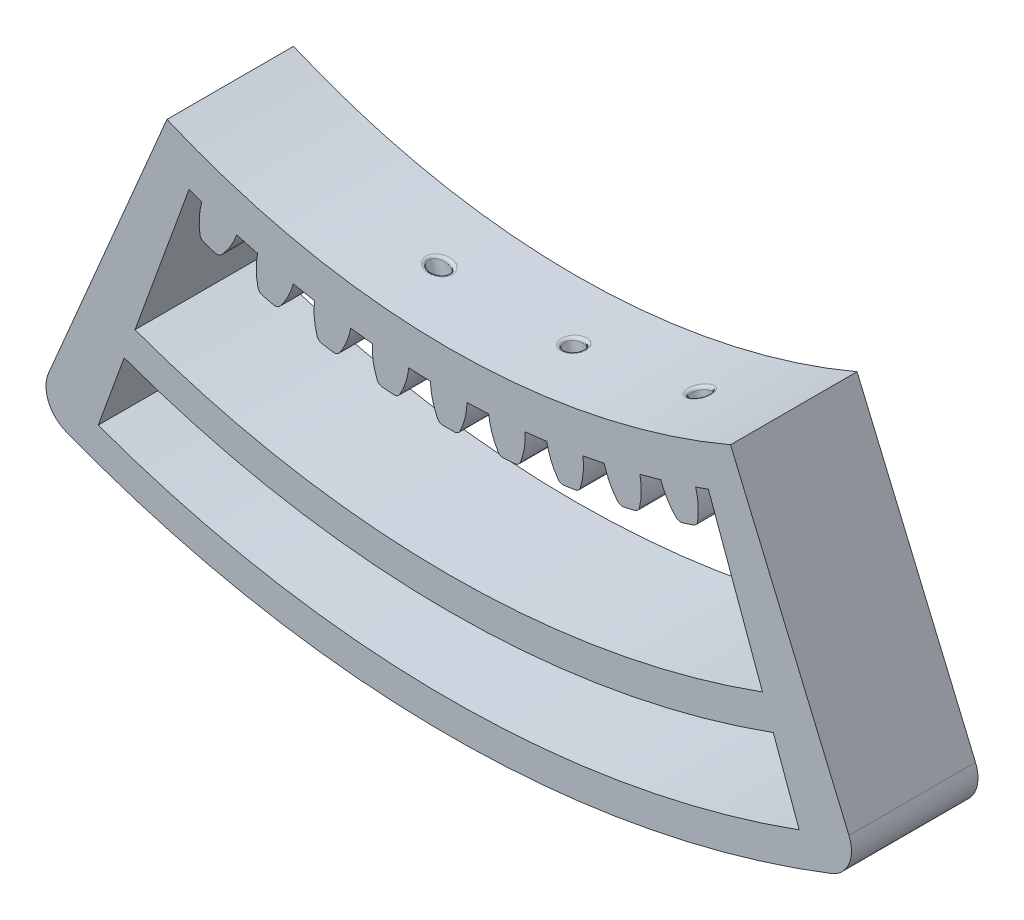
SolidWorks part; units mm, degrees
material "ABS PC"
ref_plane "Plan de face" through (0, 0, 0) normal (0, 0, 1) x (1, 0, 0)
ref_plane "Plan de dessus" through (0, 0, 0) normal (0, 1, 0) x (1, 0, 0)
ref_plane "Plan de droite" through (0, 0, 0) normal (1, 0, 0) x (0, 0, -1)
sketch "Esquisse1" plane through (0, 0, 0) normal (0, 0, 1) x (1, 0, 0)
  line L0 (-49.5929, -136.2554) -> (-41.0424, -112.7631)
  line L1 (41.0424, -112.7631) -> (49.5929, -136.2554)
  line L2 (0, 0) -> (0, -167) construction
  line L3 (-65.2521, -153.7243) -> (-44.5433, -104.9376)
  line L4 (44.5433, -104.9376) -> (65.2521, -153.7243)
  line L5 (51.303, -140.9539) -> (55.4073, -152.2302)
  line L6 (-51.303, -140.9539) -> (-55.4073, -152.2302)
  arc A0 (-65.2521, -153.7243) -> (65.2521, -153.7243) centre (0, 0) ccw
  arc A1 (-44.5433, -104.9376) -> (44.5433, -104.9376) centre (0, 0) ccw
  arc A2 (-41.0424, -112.7631) -> (41.0424, -112.7631) centre (0, 0) ccw
  arc A3 (-49.5929, -136.2554) -> (49.5929, -136.2554) centre (0, 0) ccw
  arc A4 (-55.4073, -152.2302) -> (55.4073, -152.2302) centre (0, 0) ccw
  arc A5 (-51.303, -140.9539) -> (51.303, -140.9539) centre (0, 0) ccw
  point P1 (-46.8877, -110.4606)
  point P21 (59.0684, -126.6805)
  point P22 (39.0111, -128.9523)
  dimension "D1" = 120
  dimension "D2" = 6
  dimension "D4" = 5
  dimension "D5" = 25
  dimension "D7" = 12
  dimension "D8" = 5
  dimension "D9" = 167
  dimension "D10" = 6.2825
  dimension "D3" = 40
  dimension "D6" = 3
extrude "Boss.-Extru.1" add sketch "Esquisse1" along normal mid plane 20
sketch "Esquisse18" plane through (29.868, -81.6182, 0) normal (-0.3437, 0.9391, 0) x (0.9391, 0.3437, 0)
  line L0 (-50, 0) -> (-10, 0) construction
  circle A0 centre (-50, 0) radius 1.4
  circle A1 centre (-30, 0) radius 1.4
  circle A2 centre (-10, 0) radius 1.4
  dimension "D1" = 2.8
extrude "Enlèv. mat.-Extru.1" cut sketch "Esquisse18" against normal blind 40
sketch "Esquisse2" plane through (0, 0, 10) normal (0, 0, 1) x (1, 0, 0)
  line L0 (0, -167) -> (0, -120) construction
  circle A0 centre (0, 0) radius 120 construction
  arc A1 (-65.2521, -153.7243) -> (65.2521, -153.7243) centre (0, 0) ccw construction
  arc A2 (-41.0424, -112.7631) -> (41.0424, -112.7631) centre (0, 0) ccw construction
  circle A3 centre (0, 0) radius 125 construction
  arc A4 (-2.8956, -119.9651) -> (-1.5, -124.991) centre (8.099, -119.6189) ccw
  arc A5 (2.8956, -119.9651) -> (1.5, -124.991) centre (-8.099, -119.6189) cw
  arc A6 (-1.5, -124.991) -> (1.5, -124.991) centre (0, 0) ccw
  arc A7 (-2.8956, -119.9651) -> (2.8956, -119.9651) centre (0, 0) ccw
  point P0 (0, -125)
  point P19 (-2.5, -122.5619)
  point P20 (2.5, -122.5619)
  dimension "D3" = 3
  dimension "D1" = 5
  dimension "D2" = 5
  dimension "D4" = 11
extrude "Boss.-Extru.3" add sketch "Esquisse2" against normal blind 20
fillet "Congé2" radius 1 2 edges at (1.5, -124.991, 0) (-1.5, -124.991, 0)
pattern_circular "Répétition circulaire11" count 5 every 4.4 about axis through (0, 0, 0) along (0, 0, 1) of "Congé2", "Boss.-Extru.3"
sketch "Esquisse3" plane through (0, 0, 10) normal (0, 0, 1) x (1, 0, 0)
  line L0 (0, -167) -> (0, -78.7484) construction
  line L1 (-20, -112.2319) -> (20, -112.2319)
  line L2 (-20, -112.2319) -> (-20, -102.2319)
  line L3 (-20, -102.2319) -> (20, -102.2319)
  line L4 (20, -112.2319) -> (20, -102.2319)
  arc A0 (-44.5433, -104.9376) -> (44.5433, -104.9376) centre (0, 0) ccw construction
  arc A1 (-65.2521, -153.7243) -> (65.2521, -153.7243) centre (0, 0) ccw construction
  arc A2 (-20, -112.2319) -> (20, -112.2319) centre (0, 0) ccw
  arc M11 (44.5433, -104.9376) -> (-44.5433, -104.9376) centre (0, 0) cw
  dimension "D1" = 40
  dimension "D2" = 10
pattern_circular "Répétition circulaire12" count 5 every 4.4 about axis through (0, 0, 0) along (0, 0, 1) of "Boss.-Extru.3", "Congé2"
extrude "Boss.-Extru.5" [suppressed] add sketch "Esquisse3" against normal blind 20 separate body contours L1 L0 L3 L2 | L0 L1 L4 L3 | A2 L0 L1 | L0 L1 M11
sketch "Esquisse4" [suppressed] plane through (0, 0, -10) normal (0, 0, -1) x (-1, 0, 0)
  line L0 (43.6501, -105.3122) -> (61.7891, -155.1487)
  line L1 (41.0424, -112.7631) -> (49.5929, -136.2554) construction
  line L2 (65.2521, -153.7243) -> (44.5433, -104.9376)
  line L3 (38.9903, -107.125) -> (57.1174, -156.9287) construction
  arc A0 (-44.5433, -104.9376) -> (44.5433, -104.9376) centre (0, 0) ccw construction
  arc A1 (-65.2521, -153.7243) -> (65.2521, -153.7243) centre (0, 0) ccw construction
  arc A2 (44.5433, -104.9376) -> (43.6501, -105.3122) centre (0, 0) cw
  arc A3 (61.7891, -155.1487) -> (65.2521, -153.7243) centre (0, 0) ccw
  dimension "D1" = 5
sketch "Esquisse5" [suppressed] plane through (0, 0, -10) normal (0, 0, -1) x (-1, 0, 0)
  line L0 (0, -120) -> (0, -145) construction
  line L1 (0, -150) -> (0, -162) construction
  line L2 (-55.4073, -152.2302) -> (-51.303, -140.9539) construction
  line L3 (51.303, -140.9539) -> (55.4073, -152.2302) construction
  line L4 (-41.0424, -112.7631) -> (-38.9903, -107.125)
  line L5 (-49.5929, -136.2554) -> (-41.0424, -112.7631) construction
  line L6 (-44.5433, -104.9376) -> (-65.2521, -153.7243) construction
  line L8 (44.5433, -104.9376) -> (65.2521, -153.7243)
  arc A0 (-44.5433, -104.9376) -> (44.5433, -104.9376) centre (0, 0) ccw construction
  arc A1 (-44.5433, -104.9376) -> (44.5433, -104.9376) centre (0, 0) ccw construction
  arc A2 (-46.8877, -110.4606) -> (46.8877, -110.4606) centre (0, 0) ccw construction
  arc A4 (-49.5929, -136.2554) -> (49.5929, -136.2554) centre (0, 0) ccw construction
  arc A5 (-51.303, -140.9539) -> (51.303, -140.9539) centre (0, 0) ccw construction
  arc A6 (-55.4073, -152.2302) -> (55.4073, -152.2302) centre (0, 0) ccw construction
  arc A7 (-53.3551, -146.592) -> (53.3551, -146.592) centre (0, 0) ccw construction
  arc A8 (-15.4915, -118.9959) -> (-12.0906, -119.3893) centre (0, 0) ccw construction
  point P5 (0, -132.5)
  point P22 (0, -156)
  dimension "D1" = 23.5
  dimension "D2" = 156
  dimension "D3" = 6
  dimension "D4" = 114
fillet "Congé3" radius 5 2 edges at (-65.2521, -153.7243, 0) (65.2521, -153.7243, 0)
sketch "Esquisse6" plane through (0, 0, 0) normal (1, 0, 0) x (0, 0, -1)
  line L0 (0, 0) -> (0, -120) construction
  line L1 (-10, -114) -> (10, -114)
  line L2 (-10, -114) -> (-10, -119.5826)
  line L3 (-120, 0) -> (120, 0) construction
  line L4 (10, -114) -> (10, -119.5826)
  circle A0 centre (0, 0) radius 120
  point P7 (0, -114)
  dimension "D1" = 240
  dimension "D2" = 20
  dimension "D3" = 6
sketch "Esquisse7" [suppressed] plane through (0, -104.9376, 0) normal (0, -1, 0) x (-1, 0, 0)
  line L0 (-44.5433, 0) -> (22.0827, 0) construction
  line L1 (-44.5433, -10) -> (-44.5433, 10) construction
  circle A0 centre (-7.0433, 0) radius 1.5
  circle A1 centre (12.9567, 0) radius 1.5
  circle A2 centre (-27.0433, 0) radius 1.5
  point P6 (-44.5433, 0)
  dimension "D1" = 3
  dimension "D2" = 20
  dimension "D3" = 57.5
  dimension "D4" = 20
ref_plane "Plan1" through (29.868, -81.6182, 0) normal (-0.3437, 0.9391, 0) x (0.9391, 0.3437, 0)
sketch "Esquisse19" plane through (29.868, -81.6182, 0) normal (-0.3437, 0.9391, 0) x (0.9391, 0.3437, 0)
  circle A0 centre (-50, 0) radius 1.25
  dimension "D1" = 2.5
fillet "Congé4" radius 0.5 3 edges at (-10.2419, -113.539, 0.3193) (11.0287, -113.4653, 0.3175) (30.9534, -109.7173, 0.321)
equation "\"4..50deg\"=4"
